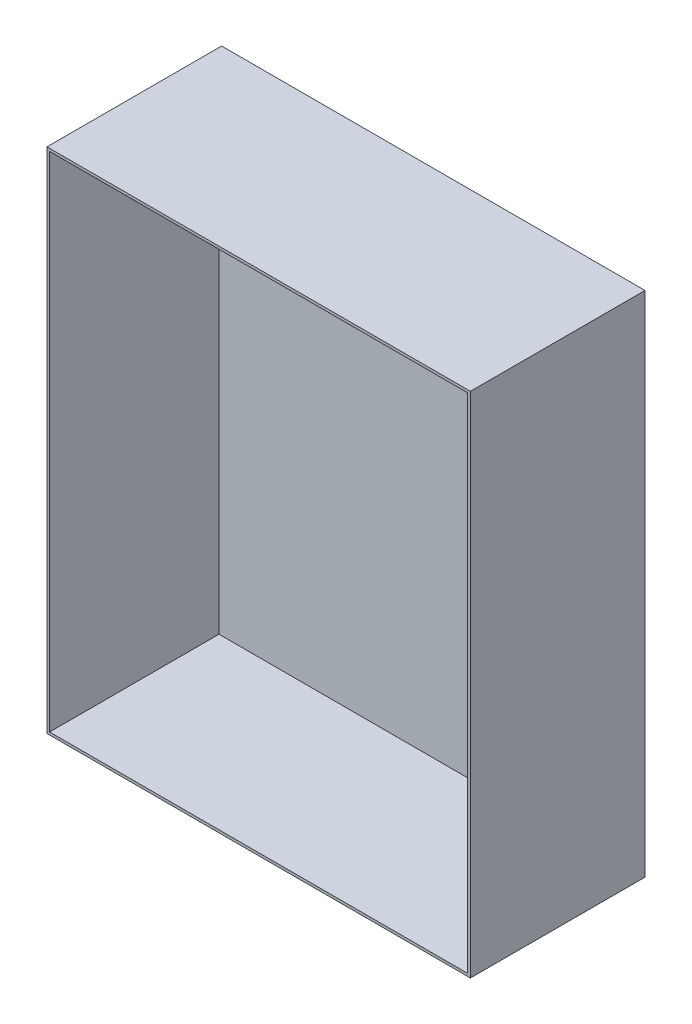
SolidWorks part; units mm, degrees
ref_plane "Front Plane" through (0, 0, 0) normal (0, 0, 1) x (1, 0, 0)
ref_plane "Top Plane" through (0, 0, 0) normal (0, 1, 0) x (1, 0, 0)
ref_plane "Right Plane" through (0, 0, 0) normal (1, 0, 0) x (0, 0, -1)
sketch "Sketch1" plane through (0, 0, 0) normal (0, 0, 1) x (1, 0, 0)
  line L1 (0, 0) -> (-127, 0)
  line L2 (0, 0) -> (0, 152.4)
  line L3 (0, 152.4) -> (-127, 152.4)
  line L4 (-127, 0) -> (-127, 152.4)
  dimension "D1" = 152.4
  dimension "D2" = 127
extrude "Boss-Extrude1" add sketch "Sketch1" along normal blind 1.5875
sketch "Sketch2" plane through (0, 0, 1.5875) normal (0, 0, 1) x (1, 0, 0)
  line L1 (-127, 152.4) -> (0, 152.4)
  line L2 (-127, 152.4) -> (-127, 0)
  line L3 (-127, 0) -> (0, 0)
  line L4 (0, 152.4) -> (0, 0)
extrude "Extrude-Thin1" add sketch "Sketch2" along normal blind 50.8 thin thin type one direction reverse wall 0.7937
